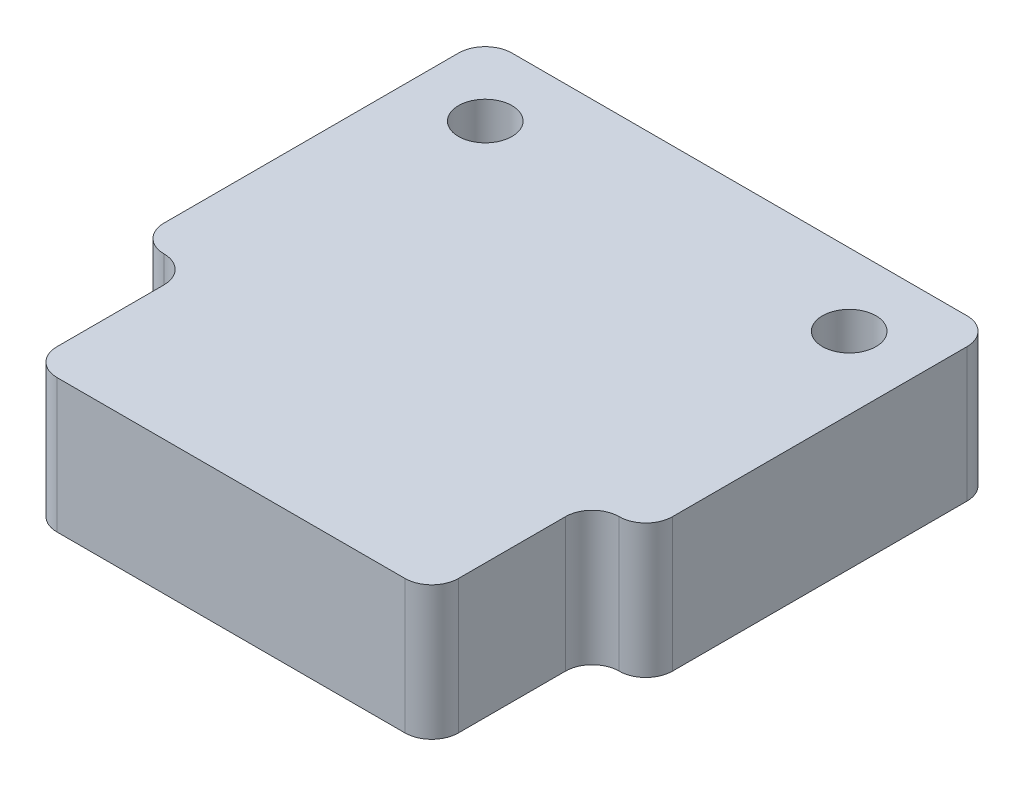
SolidWorks part; units mm, degrees
ref_plane "Plan de face" through (0, 0, 0) normal (0, 0, 1) x (1, 0, 0)
ref_plane "Plan de dessus" through (0, 0, 0) normal (0, 1, 0) x (1, 0, 0)
ref_plane "Plan de droite" through (0, 0, 0) normal (1, 0, 0) x (0, 0, -1)
sketch "Esquisse2" plane through (0, 0, 0) normal (0, 1, 0) x (1, 0, 0)
  line L0 (-9.5, -3.5) -> (-9.5, 9.5)
  line L1 (-9.5, 9.5) -> (9.5, 9.5)
  line L5 (7.5, -9.5) -> (-7.5, -9.5)
  line L6 (-7.5, -9.5) -> (-7.5, -3.5)
  line L7 (-7.5, -3.5) -> (-9.5, -3.5)
  line L8 (0, -9.5) -> (0, 9.5) construction
  line L9 (7.5, -3.5) -> (9.5, -3.5)
  line L10 (7.5, -9.5) -> (7.5, -3.5)
  line L11 (9.5, -3.5) -> (9.5, 9.5)
  circle A0 centre (-6.8, 6.8) radius 1
  circle A1 centre (6.8, 6.8) radius 1
  point P10 (0, 0)
  dimension "D4" = 2
  dimension "D1" = 2.7
  dimension "D2" = 6
  dimension "D3" = 19
  dimension "D5" = 2.7
  dimension "D6" = 2
  dimension "D7" = 19
extrude "Boss.-Extru.1" add sketch "Esquisse2" along normal blind 5
fillet "Congé1" radius 1 8 edges at (9.5, 2.5, -9.5) (9.5, 2.5, 3.5) (7.5, 2.5, 3.5) (7.5, 2.5, 9.5) (-7.5, 2.5, 9.5) (-7.5, 2.5, 3.5) (-9.5, 2.5, 3.5) (-9.5, 2.5, -9.5)
